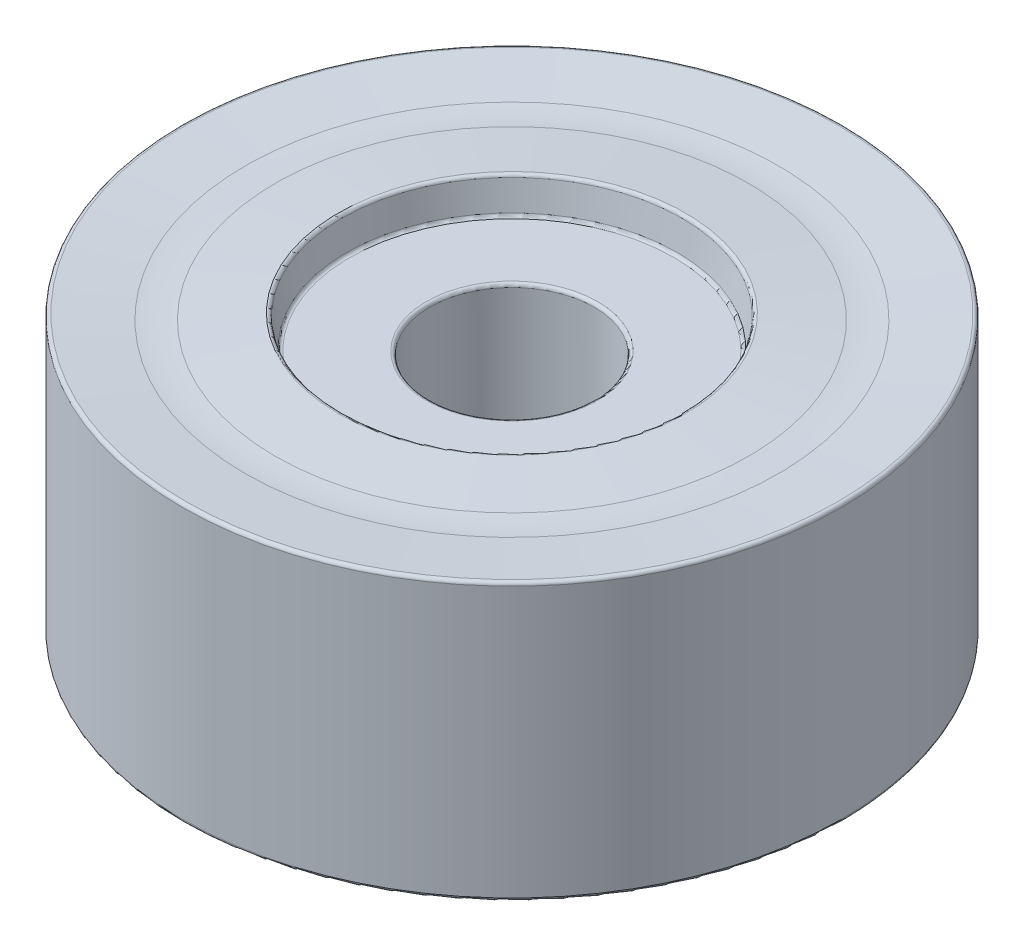
SolidWorks part; units mm, degrees
ref_plane "Płaszczyzna przednia" through (0, 0, 0) normal (0, 0, 1) x (1, 0, 0)
ref_plane "Płaszczyzna górna" through (0, 0, 0) normal (0, 1, 0) x (1, 0, 0)
ref_plane "Płaszczyzna prawa" through (0, 0, 0) normal (1, 0, 0) x (0, 0, -1)
sketch "Szkic1" plane through (0, 0, 0) normal (1, 0, 0) x (0, 0, -1)
  line L0 (0, 8.4) -> (0, 0) construction
  line L1 (2.5, 3.5) -> (6.5, 3.5)
  line L2 (6.5, 3.5) -> (6.5, 0)
  line L3 (6.5, 0) -> (10, 0)
  line L4 (10, 0) -> (10, 8.4)
  line L8 (2.5, 7.4) -> (2.5, 3.5)
  line L9 (2.5, 7.4) -> (5, 7.4)
  line L10 (5, 7.4) -> (5.1763, 8.4)
  line L11 (5.1763, 8.4) -> (7.1763, 8.2201)
  line L12 (8.0889, 8.2216) -> (10, 8.4)
  arc A1 (7.1763, 8.2201) -> (8.0889, 8.2216) centre (7.6243, 13.2) ccw
  point P12 (0, 0)
  point P15 (0, 0)
  point P16 (6.6337, 7.8989)
  point P17 (6.1857, 8.1096)
  dimension "D2" = 5
  dimension "D8" = 0.2
  dimension "D1" = 8.4
  dimension "D3" = 20
  dimension "D4" = 3.5
  dimension "D5" = 5
  dimension "D6" = 3.5
  dimension "D7" = 1
  dimension "D9" = 100
  dimension "D10" = 2.5
  dimension "D11" = 2
revolve "Obrót1" add sketch "Szkic1" angle 360 about L0
revolve "Obrót2" add sketch "Szkic1<2>" angle 360 about L0
sketch "Szkic1<2>" plane through (0, 0, 0) normal (1, 0, 0) x (0, 0, -1) same geometry as "Szkic1"
fillet "Zaokrąglenie1" radius 0.1 8 edges at (0, 0, 10) (0, 8.4, 10) (0, 8.4, 5.1763) (0, 7.4, 5) (0, 7.4, 2.5) (0, 3.5, 2.5) (0, 3.5, 6.5) (0, 0, 6.5)
